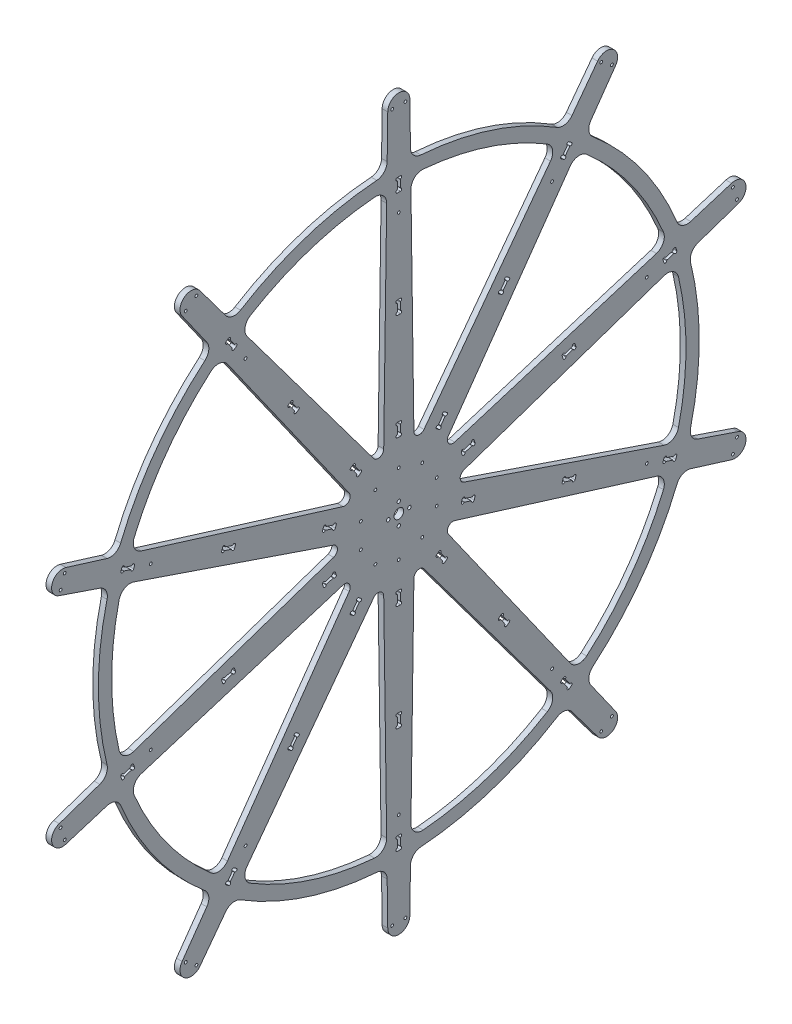
SolidWorks part; units mm, degrees
material "MDF"
ref_plane "Front Plane" through (0, 0, 0) normal (0, 0, 1) x (1, 0, 0)
ref_plane "Top Plane" through (0, 0, 0) normal (0, 1, 0) x (1, 0, 0)
ref_plane "Right Plane" through (0, 0, 0) normal (1, 0, 0) x (0, 0, -1)
sketch "Sketch1" plane through (0, 0, 0) normal (1, 0, 0) x (0, 0, -1)
  line L0 (0, 0) -> (0, -400) construction
  line L1 (-12.5, -400) -> (12.5, -400)
  line L2 (12.5, -400) -> (17.5, -41.4578)
  line L3 (-12.5, -400) -> (-17.5, -41.4578)
  line L4 (0, 0) -> (0, 12) construction
  line L5 (-1.6875, -210.2) -> (1.6875, -210.2)
  line L6 (-1.6875, -90.2) -> (1.6875, -90.2)
  line L7 (-1.6875, -90.2) -> (-1.6875, -75)
  line L8 (-1.6875, -75) -> (1.6875, -75)
  line L9 (1.6875, -90.2) -> (1.6875, -75)
  line L10 (-1.6875, -90.2) -> (1.6875, -75) construction
  line L11 (-1.6875, -75) -> (1.6875, -90.2) construction
  line L12 (-1.6875, -210.2) -> (-1.6875, -195)
  line L13 (-1.6875, -195) -> (1.6875, -195)
  line L14 (1.6875, -210.2) -> (1.6875, -195)
  line L15 (-1.6875, -210.2) -> (1.6875, -195) construction
  line L16 (-1.6875, -195) -> (1.6875, -210.2) construction
  line L17 (-1.6875, -330.2) -> (1.6875, -330.2)
  line L18 (-1.6875, -330.2) -> (-1.6875, -315)
  line L19 (-1.6875, -315) -> (1.6875, -315)
  line L20 (1.6875, -330.2) -> (1.6875, -315)
  line L21 (-1.6875, -330.2) -> (1.6875, -315) construction
  line L22 (-1.6875, -315) -> (1.6875, -330.2) construction
  line L23 (0, -82.6) -> (0, -202.6) construction
  circle A0 centre (0, 0) radius 45
  circle A1 centre (0, 0) radius 12 construction
  circle A2 centre (0, -400) radius 12.5
  circle A15 centre (1.6875, -76.5875) radius 1.5875
  circle A16 centre (-1.6875, -76.5875) radius 1.5875
  circle A17 centre (-1.6875, -88.6125) radius 1.5875
  circle A18 centre (1.6875, -88.6125) radius 1.5875
  circle A19 centre (1.6875, -196.5875) radius 1.5875
  circle A20 centre (-1.6875, -196.5875) radius 1.5875
  circle A21 centre (-1.6875, -208.6125) radius 1.5875
  circle A22 centre (1.6875, -208.6125) radius 1.5875
  circle A23 centre (1.6875, -316.5875) radius 1.5875
  circle A24 centre (-1.6875, -316.5875) radius 1.5875
  circle A25 centre (-1.6875, -328.6125) radius 1.5875
  circle A26 centre (1.6875, -328.6125) radius 1.5875
  point P8 (0, -400)
  point P12 (0, -82.6)
  point P18 (0, -322.6)
  point P19 (0, -202.6)
  point P28 (-7.5, -400)
  point P30 (7.5, -400)
  dimension "D2" = 24
  dimension "D5" = 90
  dimension "D6" = 12.5
  dimension "D13" = 3.175
  dimension "D1" = 400
  dimension "D3" = 25
  dimension "D4" = 35
  dimension "D7" = 15.2
  dimension "D8" = 3.375
  dimension "D9" = 75
  dimension "D11" = 120
  dimension "D12" = 5
  dimension "D10" = 3
extrude "Boss-Extrude1" add sketch "Sketch1" along normal mid plane 6.35 contours A0 region at (0, 0, 0)
extrude "Boss-Extrude2" add sketch "Sketch1<4>" against normal up to surface (3.175 mm away) from surface contours A0 L3 L1 L2 | L5 L14 L13 L12 | L17 L20 L19 L18 | L6 L9 L8 L7 | A2 | A0 region at (0, -220.6787, 11.3979) region at (0, -202.6, 0) region at (0, -82.6, 0) region at (0, -322.6, 0) up to face at (-3.175, 0, -45) starting at face at (3.175, 0, -45)
sketch "Sketch1<4>" plane through (0, 0, 0) normal (1, 0, 0) x (0, 0, -1) same geometry as "Sketch1"
sketch "Sketch2" plane through (0, 0, 0) normal (1, 0, 0) x (0, 0, -1)
  circle A0 centre (0, 0) radius 340
  circle A1 centre (0, 0) radius 325
  point P6 (0, -340)
  dimension "D1" = 60
  dimension "D2" = 15
extrude "Boss-Extrude3" add sketch "Sketch2" against normal up to surface (3.175 mm away) from surface contours A0 A1 region at (0, 0, 330.3833) up to face at (-3.175, -202.2395, 0) starting at face at (3.175, -202.2395, 0)
sketch "Sketch3" plane through (-3.175, 0, 0) normal (1, 0, 0) x (0, 0, -1)
  point P0 (0, 12)
extrude "Cut-Extrude1" cut sketch "Sketch1<5>" against normal through all both and the other way through all contours L18 A25 | L20 A26 | L9 L8 L7 L6 | L14 L13 L12 L5 | L20 L19 L18 L17 region at (0, -328.6125, 2.3613) region at (0, -328.6125, -2.3613)
sketch "Sketch1<5>" plane through (0, 0, 0) normal (1, 0, 0) x (0, 0, -1) same geometry as "Sketch1"
fillet "Fillet3" radius 12.7 4 edges at (0, -339.7382, -13.3404) (0, -324.7174, -13.5498) (0, -339.7382, 13.3404) (0, -324.7174, 13.5498)
fillet "Fillet4" radius 0.5 12 edges at (0, -327.025, -1.6875) (0, -318.175, -1.6875) (0, -327.025, 1.6875) (0, -318.175, 1.6875) (0, -207.025, 1.6875) (0, -198.175, 1.6875) (0, -207.025, -1.6875) (0, -198.175, -1.6875) (0, -87.025, -1.6875) (0, -87.025, 1.6875) (0, -78.175, 1.6875) (0, -78.175, -1.6875)
sketch "Sketch5" plane through (3.175, 0, 0) normal (1, 0, 0) x (0, 0, -1)
  point P0 (-7.5, -400)
  point P3 (7.5, -400)
hole_wizard "1/8 (0.125) Diameter Hole1" positions "Sketch5" profile "Sketch6" hole size "1/8" standard "ANSI Inch" end condition through all
sketch "Sketch6" plane through (3.175, -400, 7.5) normal (0, 1, 0) x (0, 0, -1)
  line L0 (0, 0) -> (0, 6.35)
  line L1 (0, 6.35) -> (1.5875, 6.35)
  line L2 (1.5875, 6.35) -> (1.5875, 0)
  line L5 (1.5875, 0) -> (0, 0)
  line L11 (0, -6.35) -> (0, 107.95) construction
  dimension "Thru Hole Dia." = 3.175
  dimension "Thru Hole Depth" = 6.35
sketch "Sketch10" plane through (-3.175, 0, 0) normal (-1, 0, 0) x (0, 0, 1)
  line L0 (0, -295.1) -> (0, -45.1) construction
  line L1 (1.5875, -43.8) -> (1.5875, -46.4) construction
  line L2 (1.5875, -293.8) -> (1.5875, -296.4) construction
  point P0 (0, -295.1)
  point P1 (0, -45.1)
  point P6 (1.5875, -45.1)
  point P9 (1.5875, -295.1)
  point P17 (0, -45.1)
  point P19 (0, -295.1)
pattern_circular "CirPattern1" count 10 over 360 about axis through (3.175, 0, 0) along (-1, 0, 0) of "Boss-Extrude2", "Cut-Extrude1", "1/8 (0.125) Diameter Hole1", "Fillet3", "Fillet4"
hole_wizard "M4 Clearance Hole1" positions "Sketch3" profile "Sketch4" hole size "M4" standard "ANSI Metric" end condition through all
sketch "Sketch4" plane through (-3.175, 12, 0) normal (0, 1, 0) x (0, 0, 1)
  line L0 (0, 0) -> (0, 6.35)
  line L1 (0, 6.35) -> (2, 6.35)
  line L2 (2, 6.35) -> (2, 0)
  line L5 (2, 0) -> (0, 0)
  line L11 (0, -6.35) -> (0, 107.95) construction
  dimension "Thru Hole Dia." = 4
  dimension "Thru Hole Depth" = 6.35
pattern_circular "CirPattern2" count 4 over 360 about axis through (-964.8402, 0, 0) along (1, 0, 0) of "M4 Clearance Hole1"
hole_wizard "1/8 (0.125) Diameter Hole2" positions "Sketch10" profile "Sketch11" hole size "1/8" standard "ANSI Inch" end condition through all
sketch "Sketch11" plane through (-3.175, -295.1, 0) normal (0, 1, 0) x (0, 0, 1)
  line L0 (0, 0) -> (0, 6.35)
  line L1 (0, 6.35) -> (1.5875, 6.35)
  line L2 (1.5875, 6.35) -> (1.5875, 0)
  line L5 (1.5875, 0) -> (0, 0)
  line L11 (0, -6.35) -> (0, 107.95) construction
  dimension "Thru Hole Dia." = 3.175
  dimension "Thru Hole Depth" = 6.35
sketch "Sketch7" plane through (3.175, 0, 0) normal (1, 0, 0) x (0, 0, -1)
  circle A0 centre (0, 0) radius 5.5
  dimension "D1" = 11
extrude "Cut-Extrude2" cut sketch "Sketch7" against normal through all both and the other way through all
fillet "Fillet1" radius 6.35 10 edges at (0, -53.3491, 17.3342) (0, -53.3491, -17.3342) (0, -32.9716, -45.3815) (0, 0, -56.0946) (0, 32.9716, -45.3815) (0, 53.3491, -17.3342) (0, 53.3491, 17.3342) (0, 32.9716, 45.3815) (0, 0, 56.0946) (0, -32.9716, 45.3815)
pattern_circular "CirPattern3" count 10 over 360 about axis through (-3.175, 0, 0) along (1, 0, 0) of "1/8 (0.125) Diameter Hole2"
equation "\"D6@Sketch1\"=\"D3@Sketch1\"/2"
